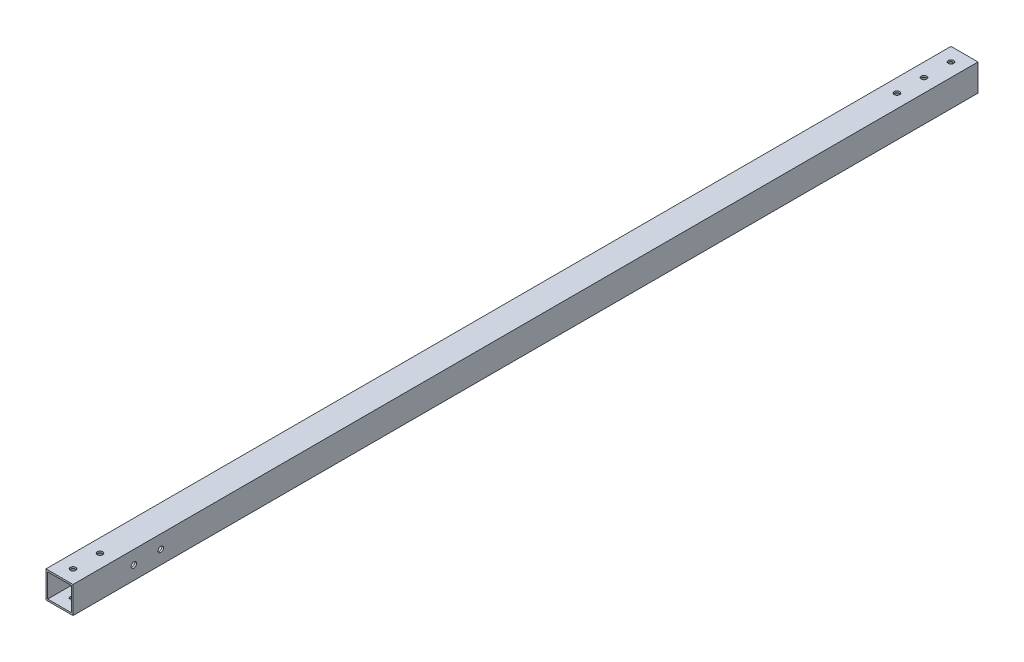
SolidWorks part; units mm, degrees
ref_plane "Front Plane" through (0, 0, 0) normal (0, 0, 1) x (1, 0, 0)
ref_plane "Top Plane" through (0, 0, 0) normal (0, 1, 0) x (1, 0, 0)
ref_plane "Right Plane" through (0, 0, 0) normal (1, 0, 0) x (0, 0, -1)
sketch "Sketch1" plane through (0, 0, 0) normal (0, 0, 1) x (1, 0, 0)
  line L1 (0, 0) -> (25.4, 0)
  line L2 (0, 0) -> (0, 25.4)
  line L3 (0, 25.4) -> (25.4, 25.4)
  line L4 (25.4, 0) -> (25.4, 25.4)
  line L5 (1.5875, 1.5875) -> (23.8125, 1.5875)
  line L6 (1.5875, 1.5875) -> (1.5875, 23.8125)
  line L7 (1.5875, 23.8125) -> (23.8125, 23.8125)
  line L8 (23.8125, 1.5875) -> (23.8125, 23.8125)
  dimension "D1" = 25.4
  dimension "D2" = 1.5875
  dimension "D3" = 1.5875
  dimension "D4" = 1.5875
  dimension "D5" = 1.5875
extrude "Boss-Extrude1" add sketch "Sketch1" along normal blind 850.9
sketch "Sketch3" plane through (0, 25.4, 0) normal (0, 1, 0) x (1, 0, 0)
  line L0 (0, -425.45) -> (25.4, -425.45) construction
  line L1 (25.4, -850.9) -> (25.4, 0) construction
  line L3 (25.4, -850.9) -> (0, -850.9) construction
  line L4 (0, -850.9) -> (0, 0) construction
  line L5 (25.4, 0) -> (0, 0) construction
  circle A12 centre (12.7, -812.8) radius 2.54
  circle A13 centre (12.7, -838.2) radius 2.54
  circle A14 centre (12.7, -12.7) radius 2.54
  circle A15 centre (12.7, -38.1) radius 2.54
  circle A16 centre (12.7, -63.5) radius 2.54
  dimension "D3" = 25.4
  dimension "D6" = 12.7
  dimension "D1" = 12.7
  dimension "D2" = 5.08
  dimension "D5" = 5.08
  dimension "D4" = 12.7
  dimension "D7" = 12.7
  dimension "D8" = 25.4
  dimension "D9" = 25.4
extrude "Cut-Extrude2" cut sketch "Sketch3" against normal through all
sketch "Sketch4" plane through (25.4, 0, 0) normal (1, 0, 0) x (0, 0, -1)
  line L0 (-850.9, 0) -> (-850.9, 25.4) construction
  circle A3 centre (-793.75, 12.7) radius 2.54
  circle A4 centre (-768.35, 12.7) radius 2.54
  dimension "D5" = 25.4
  dimension "D6" = 57.15
extrude "Cut-Extrude3" cut sketch "Sketch4" against normal through all
